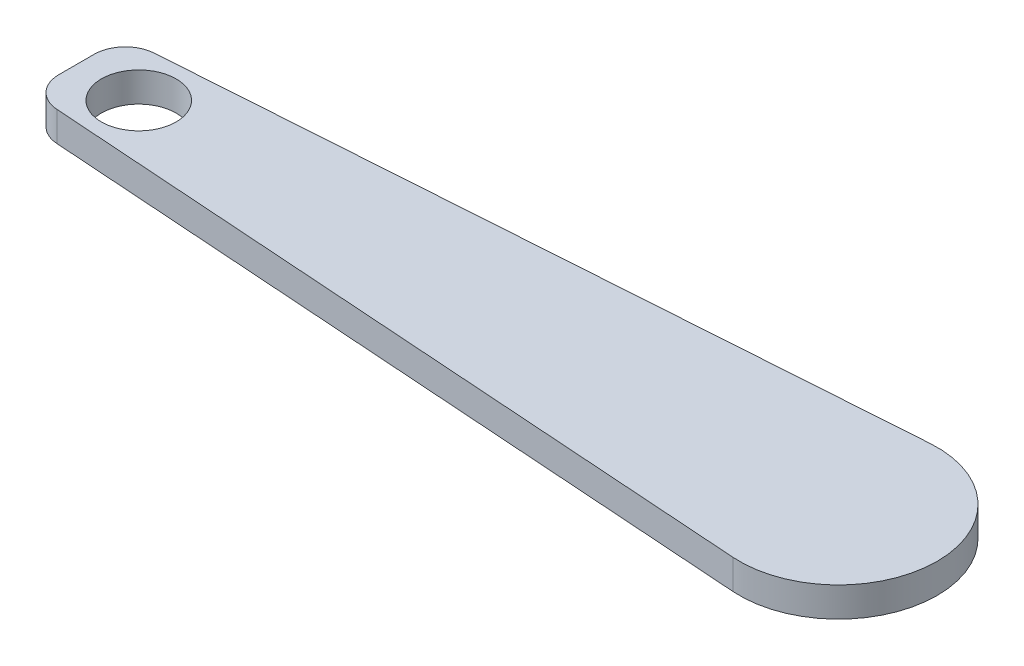
SolidWorks part; units mm, degrees
ref_plane "Front Plane" through (0, 0, 0) normal (0, 0, 1) x (1, 0, 0)
ref_plane "Top Plane" through (0, 0, 0) normal (0, 1, 0) x (1, 0, 0)
ref_plane "Right Plane" through (0, 0, 0) normal (1, 0, 0) x (0, 0, -1)
sketch "Sketch2" plane through (0, 0, 0) normal (0, 1, 0) x (1, 0, 0)
  line L0 (0, 15.9125) -> (-122.3879, 7.5)
  line L1 (-122.3879, -7.5) -> (-122.3879, 7.5)
  line L2 (-122.3879, -7.5) -> (0, -15.9125)
  line L3 (-122.3879, 0) -> (0, 0) construction
  circle A0 centre (0, 0) radius 15.875
  circle A1 centre (-112.3879, 0) radius 6
  point P8 (-122.3879, 0)
  point P15 (0, 0)
  dimension "D1" = 31.75
  dimension "D3" = 122.3879
  dimension "D2" = 12
  dimension "D5" = 10
  dimension "D6" = 15
extrude "Boss-Extrude1" add sketch "Sketch2" along normal blind 4.7625 contours L1 L3 A1 A0 L0 | L3 L1 L2 A0 A1 | A0 region at (-58.9735, 0, -6.1694) region at (10.5272, 0, -11.2756) region at (-58.9735, 0, 6.1694)
fillet "Fillet1" radius 5 2 edges at (-122.3879, 2.3813, -7.5) (-122.3879, 2.3813, 7.5)
equation "\"steeringarmlength\"=200"
equation "\"mountingholespacing\"=15"
